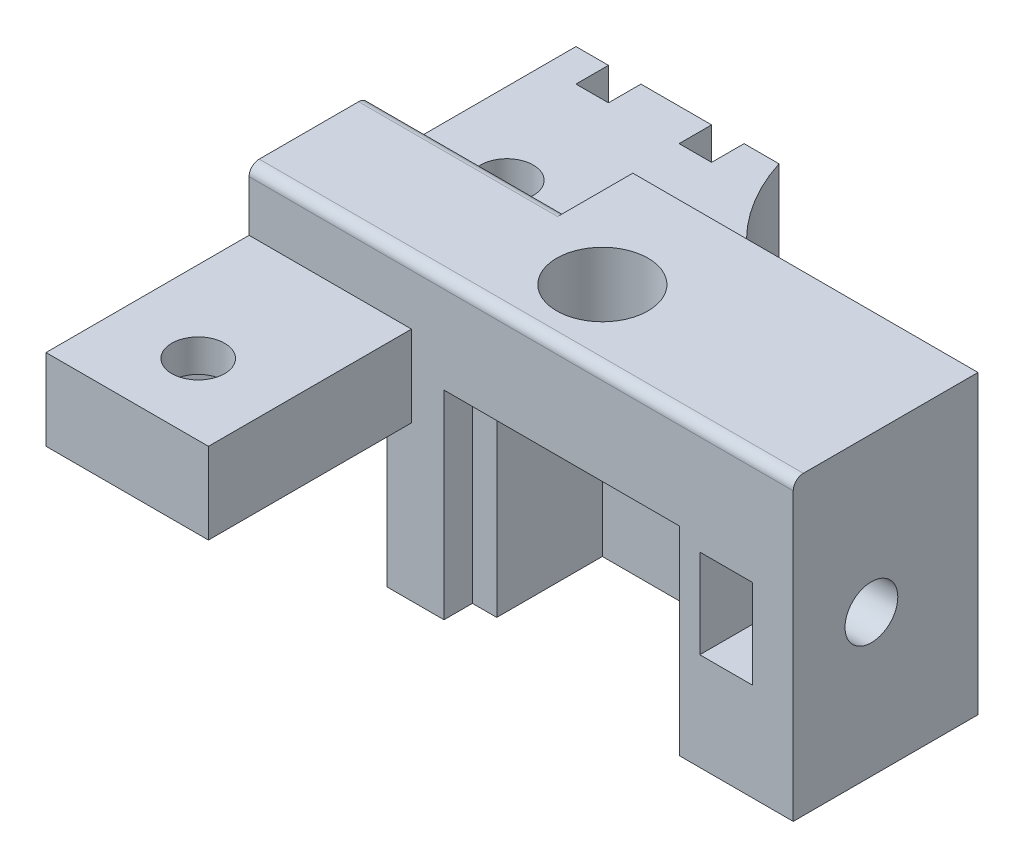
SolidWorks part; units mm, degrees
other "Markup1"
sketch "Sketch11" plane through (8.2, 17.3924, 9.55) normal (0.1833, 0.1127, 0.9766) x (0.9634, 0.1772, -0.2013)
other "Markup2"
sketch "Sketch17" plane through (-3.4, 0, 9.55) normal (-0.1941, -0.9796, 0.0517) x (0.9614, -0.1795, 0.2088)
other "Markup3"
sketch "Sketch18" plane through (-3.4, 0, -3.5) normal (0, -1, 0) x (1, 0, 0)
ref_plane "Front Plane" through (0, 0, 0) normal (0, 0, 1) x (1, 0, 0)
ref_plane "Top Plane" through (0, 0, 0) normal (0, 1, 0) x (1, 0, 0)
ref_plane "Right Plane" through (0, 0, 0) normal (1, 0, 0) x (0, 0, -1)
sketch "Sketch2" plane through (0, 0, 0) normal (0, 0, 1) x (1, 0, 0)
  line L1 (0, 0) -> (10, 0)
  line L2 (0, 0) -> (0, 7.3)
  line L3 (0, 7.3) -> (10, 7.3)
  line L4 (10, 0) -> (10, 7.3)
  dimension "D1" = 7.3
  dimension "D2" = 10
extrude "Boss-Extrude1" add sketch "Sketch2" along normal blind 4.55
sketch "Sketch3" plane through (0, 0, 4.55) normal (0, 0, 1) x (1, 0, 0)
  line L0 (0, 0) -> (10, 0) construction
  line L1 (2, 0) -> (6.6, 0)
  line L2 (2, 0) -> (2, 4.9)
  line L3 (2, 4.9) -> (6.6, 4.9)
  line L4 (6.6, 0) -> (6.6, 4.9)
  line L5 (0, 7.3) -> (0, 0) construction
  dimension "D1" = 2
  dimension "D2" = 4.6
  dimension "D3" = 4.9
extrude "Cut-Extrude1" cut sketch "Sketch3" against normal blind 3.3 contours L3 L4 L1 L2
sketch "Sketch4" plane through (0, 0, 4.55) normal (0, 0, 1) x (1, 0, 0)
  line L0 (10, 0) -> (10, 7.3) construction
  line L1 (7.7, 3.25) -> (9, 3.25)
  line L2 (7.7, 3.25) -> (7.7, 1.05)
  line L3 (7.7, 1.05) -> (9, 1.05)
  line L4 (9, 3.25) -> (9, 1.05)
  line L5 (6.6, 0) -> (10, 0) construction
  dimension "D1" = 1.3
  dimension "D2" = 2.2
  dimension "D3" = 1
  dimension "D4" = 1.05
sketch "Sketch5" plane through (0, 0, 0) normal (0, 0, 1) x (1, 0, 0)
  line L0 (0, 7.3) -> (0, 0) construction
  line L1 (-3.4, 5.8) -> (0.6, 5.8)
  line L2 (-3.4, 5.8) -> (-3.4, 3.8)
  line L3 (-3.4, 3.8) -> (0.6, 3.8)
  line L4 (0.6, 5.8) -> (0.6, 3.8)
  line L5 (10, 7.3) -> (0, 7.3) construction
  dimension "D1" = 4
  dimension "D2" = 2
  dimension "D3" = 0.6
  dimension "D4" = 1.5
extrude "Boss-Extrude2" add sketch "Sketch5" against normal blind 2.7 and the other way blind 9.55 contours L1 L4 L3 L2
sketch "Sketch13" plane through (0, 0, -2.7) normal (0, 0, -1) x (-1, 0, 0)
  line L0 (3.4, 5.8) -> (3.4, 3.8)
  line L1 (3.4, 5.8) -> (-1.6, 5.8)
  line L2 (3.4, 3.8) -> (-1.6, 3.8)
  line L3 (-1.6, 5.8) -> (-1.6, 3.8)
  dimension "D1" = 5
extrude "Boss-Extrude3" add sketch "Sketch13" against normal up to next
sketch "Sketch6" plane through (0, 0, -2.7) normal (0, 0, -1) x (-1, 0, 0)
  line L0 (3.4, 3.8) -> (-1.6, 3.8) construction
  line L1 (3.4, 5.8) -> (2.6, 5.8)
  line L2 (3.4, 5.8) -> (3.4, 3.8)
  line L3 (3.4, 3.8) -> (2.6, 3.8)
  line L4 (2.6, 5.8) -> (2.6, 3.8)
  line L5 (3.4, 5.8) -> (-1.6, 5.8) construction
  line L6 (-1.6, 5.8) -> (-0.74, 5.8)
  line L7 (-1.6, 5.8) -> (-1.6, 3.8)
  line L8 (-1.6, 3.8) -> (-0.74, 3.8)
  line L9 (-0.74, 5.8) -> (-0.74, 3.8)
  line L10 (0.06, 5.8) -> (1.8, 5.8)
  line L11 (0.06, 5.8) -> (0.06, 3.8)
  line L12 (0.06, 3.8) -> (1.8, 3.8)
  line L13 (1.8, 5.8) -> (1.8, 3.8)
  line L14 (2.6, 3.8) -> (1.8, 3.8)
  line L15 (0.06, 3.8) -> (-0.74, 3.8)
  line M6 (3.4, 5.8) -> (-1.6, 5.8)
  line M8 (-1.6, 3.8) -> (3.4, 3.8)
  line M30 (-1.6, 5.8) -> (-1.6, 3.8)
  dimension "D1" = 0.8
  dimension "D2" = 5
  dimension "D3" = 0.86
extrude "Boss-Extrude4" add sketch "Sketch6" along normal blind 0.8 contours L13 L11 M6 M8 | L9 M6 M30 M8 | L3 L2 L1 L4 region at (-0.93, 4.8, -2.7) region at (1.17, 4.8, -2.7)
fillet "Fillet1" radius 5 1 edges at (1.6, 4.8, 0)
sketch "Sketch7" plane through (0, 3.8, 0) normal (0, -1, 0) x (-1, 0, 0)
  line L0 (1.4, -7.8021) -> (1.4, -0.2021) construction
  line L1 (1.4, -7.8021) -> (1.4, -9.55) construction
  line L2 (3.4, -9.55) -> (-0.6, -9.55) construction
  line L4 (0.25, -7.1381) -> (0.25, -8.466)
  line L5 (0.25, -8.466) -> (1.4, -9.13)
  line L6 (1.4, -9.13) -> (2.55, -8.466)
  line L7 (2.55, -8.466) -> (2.55, -7.1381)
  line L8 (2.55, -7.1381) -> (1.4, -6.4742)
  line L9 (1.4, -6.4742) -> (0.25, -7.1381)
  line L10 (1.4, 1.1258) -> (0.25, 0.4619)
  line L11 (0.25, 0.4619) -> (0.25, -0.866)
  line L12 (0.25, -0.866) -> (1.4, -1.53)
  line L13 (1.4, -1.53) -> (2.55, -0.866)
  line L14 (2.55, -0.866) -> (2.55, 0.4619)
  line L15 (2.55, 0.4619) -> (1.4, 1.1258)
  circle A0 centre (1.4, -7.8021) radius 1.15 construction
  circle A1 centre (1.4, -0.2021) radius 1.15 construction
  dimension "D1" = 7.6
  dimension "D2" = 2.3
  dimension "D3" = 0.42
extrude "Cut-Extrude2" cut sketch "Sketch7" against normal blind 1.2
sketch "Sketch8" plane through (0, 5, 0) normal (0, -1, 0) x (1, 0, 0)
  circle A0 centre (-1.4, 7.8021) radius 0.65
  circle A1 centre (-1.4, 0.2021) radius 0.65
  dimension "D1" = 1.3
extrude "Cut-Extrude3" cut sketch "Sketch8" against normal through all
sketch "Sketch9" plane through (0, 4.9, 0) normal (0, -1, 0) x (1, 0, 0)
  line L0 (2, 1.25) -> (6.6, 1.25) construction
  line L4 (2, 1.25) -> (2, 4.55) construction
  circle A0 centre (3.5, 2.75) radius 1.125
  dimension "D1" = 2.25
  dimension "D2" = 1.5
  dimension "D3" = 1.5
extrude "Cut-Extrude4" cut sketch "Sketch9" against normal through all
sketch "Sketch10" plane through (10, 0, 0) normal (1, 0, 0) x (0, 0, -1)
  line L0 (-1.25, 4.9) -> (-4.55, 4.9) construction
  line L3 (-1.25, 0) -> (-1.25, 7.3) construction
  line L4 (-4.55, 0) -> (0, 0) construction
  line L5 (-1.25, 0) -> (-1.25, 4.9) construction
  line L6 (-4.55, 7.3) -> (0, 7.3) construction
  line L7 (-1.25, 3.5) -> (-4, 3.5) construction
  circle A0 centre (-2.625, 3.5) radius 0.65
  dimension "D1" = 1.3
  dimension "D3" = 1.4
  dimension "D4" = 2.75
extrude "Cut-Extrude5" cut sketch "Sketch10" against normal up to next
ref_plane "Plane1" through (9, 0, 0) normal (1, 0, 0) x (0, 0, -1)
sketch "Sketch12" plane through (9, 0, 0) normal (1, 0, 0) x (0, 0, -1)
  line L0 (-3.2572, 2.405) -> (-4.55, 2.405)
  line L1 (-1.9928, 2.405) -> (-1.3606, 3.5)
  line L2 (-1.3606, 3.5) -> (-1.9928, 4.595)
  line L3 (-1.9928, 4.595) -> (-3.2572, 4.595)
  line L4 (-3.2572, 4.595) -> (-3.8894, 3.5) construction
  line L5 (-3.8894, 3.5) -> (-3.2572, 2.405) construction
  line L6 (-3.2572, 2.405) -> (-1.9928, 2.405)
  line L7 (-4.55, 2.405) -> (-4.55, 4.595)
  line L8 (-4.55, 4.595) -> (-3.2572, 4.595)
  circle A0 centre (-2.625, 3.5) radius 1.095 construction
  dimension "D1" = 2.19
extrude "Cut-Extrude6" cut sketch "Sketch12" against normal blind 1.3
sketch "Sketch14" plane through (0, 5.8, 0) normal (0, 1, 0) x (1, 0, 0)
  line L0 (-3.4, -9.55) -> (-3.4, 3.5) construction
  line L1 (0, -4.55) -> (-3.4, -4.55)
  line L2 (0, -4.55) -> (0, -1.6021)
  line L3 (0, -1.6021) -> (-3.4, -1.6021)
  line L4 (-3.4, -4.55) -> (-3.4, -1.6021)
  line L5 (-1.4, -0.8521) -> (-1.4, -1.6021) construction
  line L6 (-1.4, -7.8021) -> (-1.4, -0.2021) construction
  line L7 (-1.4, -6.4742) -> (-1.4, -4.55) construction
  line L8 (10, -4.55) -> (0, -4.55) construction
  circle A0 centre (-1.4, -0.2021) radius 0.65 construction
  dimension "D1" = 0.75
extrude "Boss-Extrude6" add sketch "Sketch14" along normal up to surface (1.5 mm away) up to face at (3.5, 7.3, 1.625)
sketch "Sketch15" plane through (0, 7.3, 0) normal (0, 1, 0) x (1, 0, 0)
  line L0 (0, 0) -> (6.3697, 0) construction
  line L1 (0, -1.6021) -> (1.5, -1.6021)
  line L2 (0, -1.6021) -> (0, 0)
  line L3 (0, 0) -> (1.5, 0)
  line L4 (1.5, -1.6021) -> (1.5, 0)
  dimension "D1" = 1.5
extrude "Cut-Extrude7" cut sketch "Sketch15" against normal up to surface (1.5 mm away) up to face at (-1.4, 5.8, 8.4521)
fillet "Fillet2" radius 0.25 2 edges at (-0.95, 7.3, 1.6021) (3.3, 7.3, 4.55)
sketch "Sketch16" plane through (0, 0, 4.55) normal (0, 0, 1) x (1, 0, 0)
  line L0 (0, 0) -> (2, 0) construction
  line L1 (1.4, 0) -> (7.2, 0)
  line L2 (1.4, 0) -> (1.4, 4.9)
  line L3 (1.4, 4.9) -> (7.2, 4.9)
  line L4 (7.2, 0) -> (7.2, 4.9)
  line L7 (2, 4.9) -> (6.6, 4.9) construction
  line L8 (2, 0) -> (2, 4.9) construction
  point P8 (4.3, 4.9)
  dimension "D1" = 0.6
extrude "Cut-Extrude8" cut sketch "Sketch16" against normal blind 0.7
